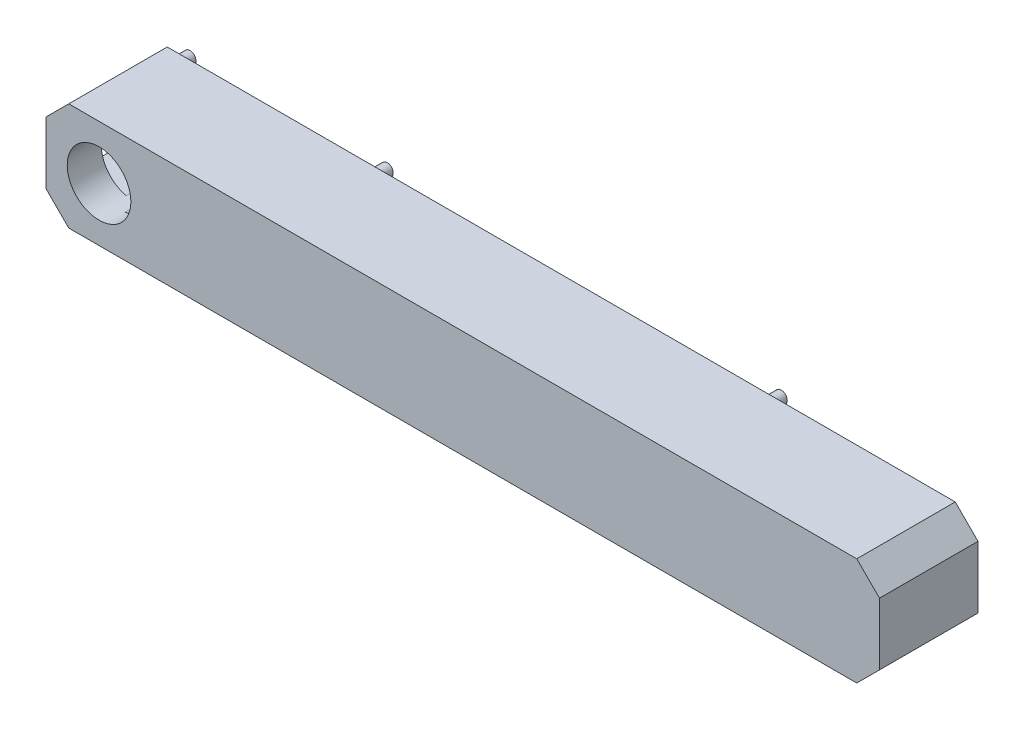
SolidWorks part; units mm, degrees
ref_plane "前视基准面" through (0, 0, 0) normal (0, 0, 1) x (1, 0, 0)
ref_plane "上视基准面" through (0, 0, 0) normal (0, 1, 0) x (1, 0, 0)
ref_plane "右视基准面" through (0, 0, 0) normal (1, 0, 0) x (0, 0, -1)
sketch "草图4" plane through (0, 0, 0) normal (0, 0, 1) x (1, 0, 0)
  line L0 (-50.0558, 0) -> (49.9442, 0)
  line L2 (-50.0558, -8.2) -> (49.9442, -8.2)
  line L3 (49.9442, -8.2) -> (49.9442, 0)
  line L4 (52.9442, 0) -> (52.9442, -8.2)
  line L6 (49.9442, 3) -> (-54.0558, 3)
  line L9 (49.9442, -11.2) -> (-54.0558, -11.2)
  line L10 (-57.0558, -8.2) -> (-57.0558, 0)
  line L13 (-54.0558, 3) -> (-57.0558, 0)
  line L14 (49.9442, 3) -> (52.9442, 0)
  line L15 (-57.0558, -8.2) -> (-54.0558, -11.2)
  line L16 (52.9442, -8.2) -> (49.9442, -11.2)
  circle A0 centre (-50.0558, -4.1) radius 4.2
extrude "凸台-拉伸5" add sketch "草图4" along normal blind 2.5 contours A0 L2 L3 L0 | L16 L4 L14 L6 L13 L10 L15 L9 A0 L0 L3 L2 region at (1.6226, -4.1, 0) region at (51.8351, -4.1, 0)
extrude "凸台-拉伸6" add sketch "草图4<6>" against normal blind 10.5 contours L16 L4 L14 L6 L13 L10 L15 L9 A0 L0 L3 L2 region at (51.8351, -4.1, 0)
sketch "草图4<6>" plane through (0, 0, 0) normal (0, 0, 1) x (1, 0, 0) same geometry as "草图4"
sketch "草图5" plane through (0, 0, -10.5) normal (0, 0, -1) x (-1, 0, 0)
sketch "草图6" plane through (0, 0, -10.5) normal (0, 0, -1) x (-1, 0, 0)
  line L0 (0.0558, 0) -> (0.0558, 3)
  circle A0 centre (0.0558, 1.5) radius 1
extrude "切除-拉伸2" cut sketch "草图6" against normal blind 2 contours A0
sketch "草图7" plane through (0, 0, -10.5) normal (0, 0, -1) x (-1, 0, 0)
  line L0 (-0.3997, -8.2) -> (-0.3997, -11.2)
  line L1 (49.1448, -8.2) -> (-49.9442, -8.2) construction
  line L2 (-49.9442, -11.2) -> (54.0558, -11.2) construction
  circle A0 centre (-0.3997, -9.7) radius 0.8
extrude "凸台-拉伸7" add sketch "草图7" along normal blind 2 contours L0 A0 | L0 A0 region at (0.0602, -9.7, -10.5) region at (0.7393, -9.7, -10.5)
sketch "草图8" plane through (0, 0, -10.5) normal (0, 0, -1) x (-1, 0, 0)
  line L0 (-49.9442, 3) -> (0, 0)
  line L1 (0, 0) -> (54.0558, 3)
  circle A0 centre (-24.9721, 1.5) radius 0.8
  circle A1 centre (27.0279, 1.5) radius 0.8
extrude "凸台-拉伸8" add sketch "草图8" along normal blind 2 contours L0 A0 | L0 A0 | A1 region at (24.9517, 1.8389, -10.5) region at (24.9925, 1.1611, -10.5)
sketch "草图9" plane through (0, 0, -10.5) normal (0, 0, -1) x (-1, 0, 0)
  line L0 (-0.3997, -8.2) -> (-49.9442, -11.2)
  line L1 (49.1448, -8.2) -> (-49.9442, -8.2) construction
  line L2 (-0.3997, -8.2) -> (54.0558, -11.2)
  circle A0 centre (-25.172, -9.7) radius 1
  circle A1 centre (26.828, -9.7) radius 1
extrude "切除-拉伸3" cut sketch "草图9" against normal blind 2 contours L0 A0 | L0 A0 | L2 A1 | L2 A1 region at (25.1463, -10.1236, -10.5) region at (25.1976, -9.2764, -10.5) region at (-26.8514, -9.2762, -10.5) region at (-26.8047, -10.1238, -10.5)
sketch "草图10" plane through (52.9442, 0, 0) normal (1, 0, 0) x (0, 0, -1)
  line L0 (10.5, -4.1) -> (10.5, -1.6)
  line L1 (10.5, 0) -> (10.5, -8.2) construction
  line L3 (7.5, -4.1) -> (7.5, -2.5)
  line L4 (7.5, -4.1) -> (7.5, -5.7)
  line L5 (10.5, -4.1) -> (10.5, -6.6)
  line L6 (7.5, -2.5) -> (10.5, -1.6)
  line L7 (7.5, -5.7) -> (10.5, -6.6)
sketch "草图11" plane through (-57.0558, 0, 0) normal (-1, 0, 0) x (0, 0, 1)
  line L1 (0, 0) -> (0, -8.2)
  line L3 (-10.5, -1.6) -> (-10.5, -6.6)
  line L4 (2.5, -8.2) -> (-10.5, -8.2) construction
  line L5 (0, 0) -> (-10.5, 0)
  line L6 (-10.5, 0) -> (-10.5, -8.2)
  line L7 (-10.5, -8.2) -> (-10.5, 0) construction
  line L8 (-10.5, -8.2) -> (0, -8.2)
  line M5 (2.5, 0) -> (-10.5, 0)
  line M6 (-10.5, 0) -> (-10.5, -8.2)
  line M7 (-10.5, -8.2) -> (2.5, -8.2)
extrude "切除-拉伸6" cut sketch "草图11" against normal blind 5 contours L1 M5 M6 M7 region at (-57.0558, -4.1, -5.25)
sketch "草图12" plane through (0, 0, -10.5) normal (0, 0, -1) x (-1, 0, 0)
  line L0 (52.0558, -0.4068) -> (57.0558, 0)
  line L1 (52.0558, -0.4068) -> (52.0558, 0)
  line L2 (52.0558, 0) -> (57.0558, 0)
extrude "凸台-拉伸9" add sketch "草图12" against normal blind 11
sketch "草图13" plane through (0, 0, -10.5) normal (0, 0, -1) x (-1, 0, 0)
  line L0 (52.0558, -7.7932) -> (52.0558, -8.2)
  line L1 (52.0558, -8.2) -> (57.0558, -8.2)
  line L2 (57.0558, -8.2) -> (52.0558, -7.7932)
extrude "凸台-拉伸10" add sketch "草图13" against normal blind 11
sketch "草图14" plane through (0, 0, 0) normal (0, 0, -1) x (-1, 0, 0)
sketch "草图15" plane through (0, 0, 0) normal (0, 0, -1) x (-1, 0, 0)
  line L0 (52.0558, -0.4068) -> (57.0558, 0)
  line L1 (57.0558, 0) -> (57.0558, -8.2)
  line L2 (57.0558, -8.2) -> (52.0558, -7.7932)
  arc A0 (52.0558, -7.7932) -> (52.0558, -0.4068) centre (50.0558, -4.1) ccw
extrude "凸台-拉伸11" add sketch "草图15" along normal blind 2 contours A0 L0 L1 L2
sketch "草图18" plane through (0, 0, -10.5) normal (0, 0, -1) x (-1, 0, 0)
  line L0 (52.0558, -7.7932) -> (54.0558, -11.2)
  circle A0 centre (53.0558, -9.4966) radius 1
extrude "切除-拉伸7" cut sketch "草图18" against normal blind 2 contours L0 A0 | L0 A0 region at (-53.4218, -9.2818, -10.5) region at (-52.6898, -9.7115, -10.5)
sketch "草图19" plane through (0, 0, -10.5) normal (0, 0, -1) x (-1, 0, 0)
  line L0 (52.0558, -0.4068) -> (54.0558, 3)
  line L1 (52.0558, -0.4068) -> (57.0558, 0) construction
  arc A0 (52.0558, -7.7932) -> (52.0558, -0.4068) centre (50.0558, -4.1) ccw construction
  circle A1 centre (53.0558, 1.2966) radius 0.8
extrude "凸台-拉伸13" add sketch "草图19" along normal blind 2 contours A1
sketch "草图20" plane through (-57.0558, 0, 0) normal (-1, 0, 0) x (0, 0, 1)
  line L0 (-10.5, 0) -> (-2, 0)
  line L1 (-2, 0) -> (-2, -8.2)
  line L2 (-2, -8.2) -> (-10.5, -8.2)
  line L3 (-10.5, -8.2) -> (-10.5, 0)
extrude "切除-拉伸8" cut sketch "草图20" against normal blind 10
